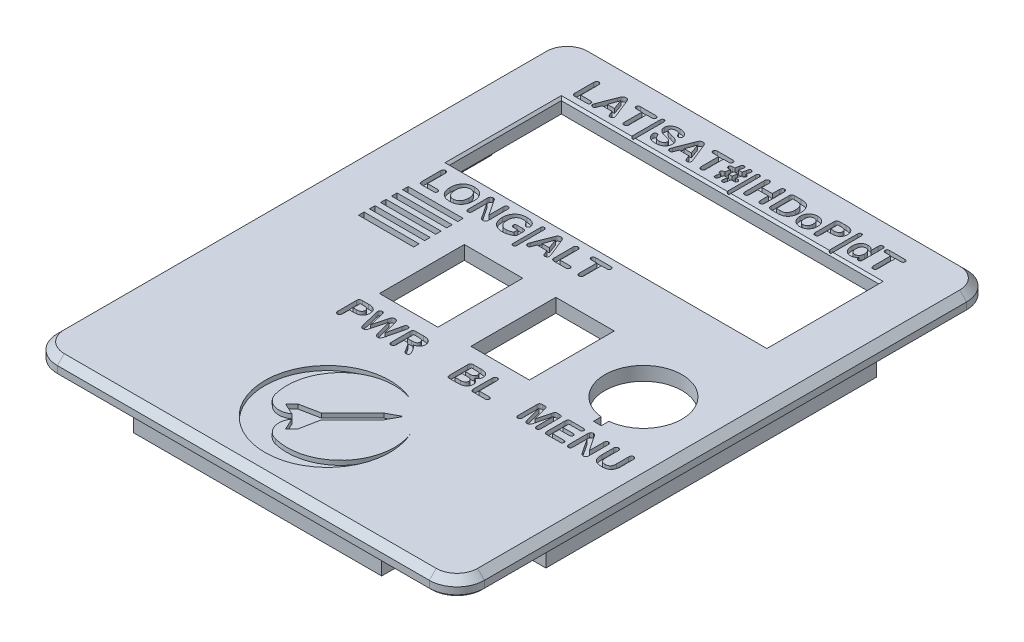
SolidWorks part; units mm, degrees
ref_plane "Front Plane" through (0, 0, 0) normal (0, 0, 1) x (1, 0, 0)
ref_plane "Top Plane" through (0, 0, 0) normal (0, 1, 0) x (1, 0, 0)
ref_plane "Right Plane" through (0, 0, 0) normal (1, 0, 0) x (0, 0, -1)
sketch "Sketch1" plane through (0, 0, 0) normal (0, 1, 0) x (1, 0, 0)
  line L1 (42.8625, -61.9125) -> (-42.8625, -61.9125)
  line L2 (49.2125, -55.5625) -> (49.2125, 55.5625)
  line L3 (42.8625, 61.9125) -> (-42.8625, 61.9125)
  line L4 (-49.2125, -55.5625) -> (-49.2125, 55.5625)
  line L5 (49.2125, -61.9125) -> (-49.2125, 61.9125) construction
  line L6 (49.2125, 61.9125) -> (-49.2125, -61.9125) construction
  arc A0 (-42.8625, -61.9125) -> (-49.2125, -55.5625) centre (-42.8625, -55.5625) cw
  arc A1 (42.8625, -61.9125) -> (49.2125, -55.5625) centre (42.8625, -55.5625) ccw
  arc A2 (49.2125, 55.5625) -> (42.8625, 61.9125) centre (42.8625, 55.5625) ccw
  arc A3 (-42.8625, 61.9125) -> (-49.2125, 55.5625) centre (-42.8625, 55.5625) ccw
  point P0 (0, 0)
  dimension "D3" = 6.35
  dimension "D1" = 123.825
  dimension "D2" = 98.425
extrude "Main Body" add sketch "Sketch1" along normal blind 3.175
chamfer "Chamfer1" distance 1.5875 angle 45 8 edges at (-49.2125, 3.175, 0) (-47.3526, 3.175, -60.0526) (0, 3.175, -61.9125) (47.3526, 3.175, -60.0526) (49.2125, 3.175, 0) (47.3526, 3.175, 60.0526) (0, 3.175, 61.9125) (-47.3526, 3.175, 60.0526)
sketch "Sketch2" plane through (0, 3.175, 0) normal (0, 1, 0) x (1, 0, 0)
  line L0 (0, 35.052) -> (0, 60.325) construction
  line L1 (42.8625, 60.325) -> (-42.8625, 60.325) construction
  line L3 (-42.8625, 61.9125) -> (42.8625, 61.9125) construction
  line L4 (36.576, 22.1615) -> (-36.576, 22.1615)
  line L5 (36.576, 22.1615) -> (36.576, 47.9425)
  line L6 (36.576, 47.9425) -> (-36.576, 47.9425)
  line L7 (-36.576, 22.1615) -> (-36.576, 47.9425)
  line L8 (36.576, 22.1615) -> (-36.576, 47.9425) construction
  line L9 (36.576, 47.9425) -> (-36.576, 22.1615) construction
  line L10 (-36.576, 8.8265) -> (-23.876, 8.8265)
  line L11 (-36.576, 11.3665) -> (-23.876, 11.3665)
  line L12 (-36.576, 11.3665) -> (-36.576, 12.6365)
  line L13 (-36.576, 12.6365) -> (-23.876, 12.6365)
  line L14 (-23.876, 11.3665) -> (-23.876, 12.6365)
  line L15 (-36.576, 11.3665) -> (-23.876, 12.6365) construction
  line L16 (-36.576, 12.6365) -> (-23.876, 11.3665) construction
  line L17 (-36.576, 8.8265) -> (-36.576, 10.0965)
  line L18 (-36.576, 10.0965) -> (-23.876, 10.0965)
  line L19 (-23.876, 8.8265) -> (-23.876, 10.0965)
  line L20 (-36.576, 8.8265) -> (-23.876, 10.0965) construction
  line L21 (-36.576, 10.0965) -> (-23.876, 8.8265) construction
  line L22 (-36.576, 6.2865) -> (-23.876, 6.2865)
  line L23 (-36.576, 6.2865) -> (-36.576, 7.5565)
  line L24 (-36.576, 7.5565) -> (-23.876, 7.5565)
  line L25 (-23.876, 6.2865) -> (-23.876, 7.5565)
  line L26 (-36.576, 6.2865) -> (-23.876, 7.5565) construction
  line L27 (-36.576, 7.5565) -> (-23.876, 6.2865) construction
  line L28 (-36.576, 3.7465) -> (-23.876, 3.7465)
  line L29 (-36.576, 3.7465) -> (-36.576, 5.0165)
  line L30 (-36.576, 5.0165) -> (-23.876, 5.0165)
  line L31 (-23.876, 3.7465) -> (-23.876, 5.0165)
  line L32 (-36.576, 3.7465) -> (-23.876, 5.0165) construction
  line L33 (-36.576, 5.0165) -> (-23.876, 3.7465) construction
  line L34 (-36.576, 1.2065) -> (-23.876, 1.2065)
  line L35 (-36.576, 1.2065) -> (-36.576, 2.4765)
  line L36 (-36.576, 2.4765) -> (-23.876, 2.4765)
  line L37 (-23.876, 1.2065) -> (-23.876, 2.4765)
  line L38 (-36.576, 1.2065) -> (-23.876, 2.4765) construction
  line L39 (-36.576, 2.4765) -> (-23.876, 1.2065) construction
  line L40 (-18.542, -2.2225) -> (32.512, -2.2225) construction
  line L41 (-18.542, 7.5565) -> (-5.08, 7.5565)
  line L42 (-18.542, 7.5565) -> (-18.542, -12.0015)
  line L43 (-18.542, -12.0015) -> (-5.08, -12.0015)
  line L44 (-5.08, 7.5565) -> (-5.08, -12.0015)
  line L45 (2.54, 7.5565) -> (16.002, 7.5565)
  line L46 (2.54, 7.5565) -> (2.54, -12.0015)
  line L47 (2.54, -12.0015) -> (16.002, -12.0015)
  line L48 (16.002, 7.5565) -> (16.002, -12.0015)
  line L49 (32.512, -2.2225) -> (32.512, -11.1125) construction
  line L50 (33.401, -11.0679) -> (33.401, -12.8459)
  line L51 (33.401, -12.8459) -> (31.623, -12.8459)
  line L52 (31.623, -12.8459) -> (31.623, -11.0679)
  line L53 (-1.27, -60.325) -> (-1.27, 7.5565) construction
  line L54 (-42.8625, -60.325) -> (42.8625, -60.325) construction
  arc A0 (33.401, -11.0679) -> (31.623, -11.0679) centre (32.512, -2.2225) ccw
  point P6 (0, 35.052)
  point P13 (-30.226, 12.0015)
  point P19 (-30.226, 9.4615)
  point P24 (-30.226, 6.9215)
  point P29 (-30.226, 4.3815)
  point P34 (-30.226, 1.8415)
  point P55 (0, -60.325)
  dimension "D12" = 17.78
  dimension "D1" = 73.152
  dimension "D2" = 25.781
  dimension "D3" = 13.97
  dimension "D4" = 1.27
  dimension "D5" = 12.7
  dimension "D6" = 9.525
  dimension "D8" = 19.558
  dimension "D9" = 13.462
  dimension "D10" = 7.62
  dimension "D11" = 14.605
  dimension "D13" = 16.51
  dimension "D14" = 1.778
  dimension "D15" = 2.54
  dimension "D7" = 5
extrude "LCD & Switch Cutouts" cut sketch "Sketch2" against normal through all
sketch "Sketch4" plane through (0, 0, 0) normal (0, -1, 0) x (1, 0, 0)
  line L28 (-47.4345, 55.5625) -> (-47.4345, -55.5625)
  line L29 (-42.8625, -60.1345) -> (42.8625, -60.1345)
  line L30 (47.4345, -55.5625) -> (47.4345, 55.5625)
  line L31 (42.8625, 60.1345) -> (-42.8625, 60.1345)
  line L32 (-47.4345, 55.5625) -> (-47.4345, -55.5625)
  line L33 (-42.8625, -60.1345) -> (42.8625, -60.1345)
  line L34 (47.4345, -55.5625) -> (47.4345, 55.5625)
  line L35 (42.8625, 60.1345) -> (-42.8625, 60.1345)
  line L40 (-48.7045, 55.5625) -> (-48.7045, -55.5625)
  line L41 (-42.8625, -61.4045) -> (42.8625, -61.4045)
  line L42 (48.7045, -55.5625) -> (48.7045, 55.5625)
  line L43 (42.8625, 61.4045) -> (-42.8625, 61.4045)
  line L44 (-48.7045, 55.5625) -> (-48.7045, -55.5625)
  line L45 (-42.8625, -61.4045) -> (42.8625, -61.4045)
  line L46 (48.7045, -55.5625) -> (48.7045, 55.5625)
  line L47 (42.8625, 61.4045) -> (-42.8625, 61.4045)
  arc A28 (-42.8625, 60.1345) -> (-47.4345, 55.5625) centre (-42.8625, 55.5625) ccw
  arc A29 (-47.4345, -55.5625) -> (-42.8625, -60.1345) centre (-42.8625, -55.5625) ccw
  arc A30 (42.8625, -60.1345) -> (47.4345, -55.5625) centre (42.8625, -55.5625) ccw
  arc A31 (47.4345, 55.5625) -> (42.8625, 60.1345) centre (42.8625, 55.5625) ccw
  arc A32 (-42.8625, 60.1345) -> (-47.4345, 55.5625) centre (-42.8625, 55.5625) ccw
  arc A33 (-47.4345, -55.5625) -> (-42.8625, -60.1345) centre (-42.8625, -55.5625) ccw
  arc A34 (42.8625, -60.1345) -> (47.4345, -55.5625) centre (42.8625, -55.5625) ccw
  arc A35 (47.4345, 55.5625) -> (42.8625, 60.1345) centre (42.8625, 55.5625) ccw
  arc A40 (-42.8625, 61.4045) -> (-48.7045, 55.5625) centre (-42.8625, 55.5625) ccw
  arc A41 (-48.7045, -55.5625) -> (-42.8625, -61.4045) centre (-42.8625, -55.5625) ccw
  arc A42 (42.8625, -61.4045) -> (48.7045, -55.5625) centre (42.8625, -55.5625) ccw
  arc A43 (48.7045, 55.5625) -> (42.8625, 61.4045) centre (42.8625, 55.5625) ccw
  arc A44 (-42.8625, 61.4045) -> (-48.7045, 55.5625) centre (-42.8625, 55.5625) ccw
  arc A45 (-48.7045, -55.5625) -> (-42.8625, -61.4045) centre (-42.8625, -55.5625) ccw
  arc A46 (42.8625, -61.4045) -> (48.7045, -55.5625) centre (42.8625, -55.5625) ccw
  arc A47 (48.7045, 55.5625) -> (42.8625, 61.4045) centre (42.8625, 55.5625) ccw
  dimension "D1" = 1.778
  dimension "D2" = 0.508
extrude "Gap Ring" add sketch "Sketch4" along normal blind 0.508
sketch "Sketch6" plane through (0, 3.175, 0) normal (0, 1, 0) x (1, 0, 0)
  line L0 (-36.576, 49.8475) -> (36.576, 49.8475) construction
  line L1 (-36.576, 47.9425) -> (-36.576, 22.1615) construction
  line L2 (36.576, 22.1615) -> (36.576, 47.9425) construction
  line L3 (36.576, 47.9425) -> (-36.576, 47.9425) construction
  line L4 (-18.542, -12.0015) -> (-5.08, -12.0015) construction
  line L5 (-36.576, 14.5415) -> (36.576, 14.5415) construction
  line L6 (-36.576, 22.1615) -> (36.576, 22.1615) construction
  line L7 (-20.447, -20.8915) -> (41.402, -20.8915) construction
  arc A1 (33.401, -11.0679) -> (31.623, -11.0679) centre (32.512, -2.2225) ccw construction
  text T0 "LAT|SAT#|HDoP|dT" font "Arial Rounded MT Bold" height 5.715
  text T1 "LONG|ALT" font "Arial Rounded MT Bold" height 5.715
  text T2 "PWR    BL   MENU" font "Arial Rounded MT Bold" height 5.715
  point P16 (0, 0)
  point P20 (41.402, -2.2225)
  point P24 (0, 0)
  point P27 (0, 0)
  point P29 (-20.9004, -20.8915)
  dimension "D1" = 1.905
  dimension "D2" = 7.62
  dimension "D3" = 8.89
  dimension "D4" = 1.905
extrude "Text" cut sketch "Sketch6" against normal blind 1.016
sketch "Sketch7" plane through (30.0839, 3.175, 12.4611) normal (0, 1, 0) x (0.7071, 0, 0.7071)
  line L0 (0, 0) -> (0, -60.325) construction
  line L2 (0, -30.1625) -> (-0.9525, -33.3375)
  line L3 (-0.9525, -33.3375) -> (-0.9525, -43.4975)
  line L4 (-0.9525, -43.4975) -> (-3.4925, -47.3075)
  line L5 (-3.4925, -47.3075) -> (-3.4925, -49.3395)
  line L6 (-3.4925, -49.3395) -> (-0.762, -48.3466)
  line L7 (0, -30.1625) -> (0.9525, -33.3375)
  line L8 (0.9525, -33.3375) -> (0.9525, -43.4975)
  line L9 (0.9525, -43.4975) -> (3.4925, -47.3075)
  line L10 (3.4925, -47.3075) -> (3.4925, -49.3395)
  line L11 (3.4925, -49.3395) -> (0.762, -48.3466)
  arc A0 (-5.08, -29.084) -> (5.08, -29.084) centre (0, -42.545) ccw
  arc A1 (-5.08, -29.084) -> (-6.35, -51.0068) centre (0, -40.3765) ccw
  arc A2 (-0.762, -48.3466) -> (-6.35, -51.0068) centre (-4.4428, -47.814) cw
  arc A3 (0.762, -48.3466) -> (6.35, -51.0068) centre (4.4428, -47.814) ccw
  arc A4 (6.35, -51.0068) -> (5.08, -29.084) centre (0, -40.3765) ccw
  dimension "D4" = 12.3825
  dimension "D12" = 0.762
  dimension "D3" = 10.16
  dimension "D5" = 0.9525
  dimension "D6" = 3.175
  dimension "D7" = 2.032
  dimension "D8" = 10.16
  dimension "D9" = 2.54
  dimension "D10" = 3.81
  dimension "D13" = 6.35
extrude "Logo" cut sketch "Sketch7" against normal blind 1.016
chamfer "Chamfer2" distance 0.508 angle 45 4 edges at (36.576, 3.175, -35.052) (0, 3.175, -22.1615) (-36.576, 3.175, -35.052) (0, 3.175, -47.9425)
sketch "Sketch8" plane through (0, 0, 0) normal (0, -1, 0) x (1, 0, 0)
  line L0 (-49.2125, -55.5625) -> (-49.2125, 55.5625) construction
  line L1 (-45.9105, 38.1) -> (-42.7355, 38.1)
  line L2 (-45.9105, 38.1) -> (-45.9105, -38.1)
  line L3 (-45.9105, -38.1) -> (-42.7355, -38.1)
  line L4 (-42.7355, 38.1) -> (-42.7355, -38.1)
  line L5 (-28.575, 58.6105) -> (28.575, 58.6105)
  line L6 (-28.575, 58.6105) -> (-28.575, 55.4355)
  line L7 (-28.575, 55.4355) -> (28.575, 55.4355)
  line L8 (28.575, 58.6105) -> (28.575, 55.4355)
  line L9 (-42.8625, 61.9125) -> (42.8625, 61.9125) construction
  line L10 (0, 0) -> (47.4345, 0) construction
  line L11 (47.4345, -55.5625) -> (47.4345, 55.5625) construction
  line L12 (0, 0) -> (0, -60.1345) construction
  line L13 (-42.8625, -60.1345) -> (42.8625, -60.1345) construction
  line L14 (42.7355, 38.1) -> (42.7355, -38.1)
  line L15 (45.9105, -38.1) -> (42.7355, -38.1)
  line L16 (45.9105, 38.1) -> (45.9105, -38.1)
  line L17 (45.9105, 38.1) -> (42.7355, 38.1)
  line L18 (28.575, -58.6105) -> (28.575, -55.4355)
  line L19 (-28.575, -55.4355) -> (28.575, -55.4355)
  line L20 (-28.575, -58.6105) -> (-28.575, -55.4355)
  line L21 (-28.575, -58.6105) -> (28.575, -58.6105)
  dimension "D1" = 3.302
  dimension "D2" = 3.175
  dimension "D3" = 76.2
  dimension "D4" = 38.1
  dimension "D5" = 57.15
  dimension "D6" = 3.302
  dimension "D7" = 3.175
  dimension "D8" = 28.575
extrude "Boss-Extrude3" add sketch "Sketch8" along normal blind 6.35
